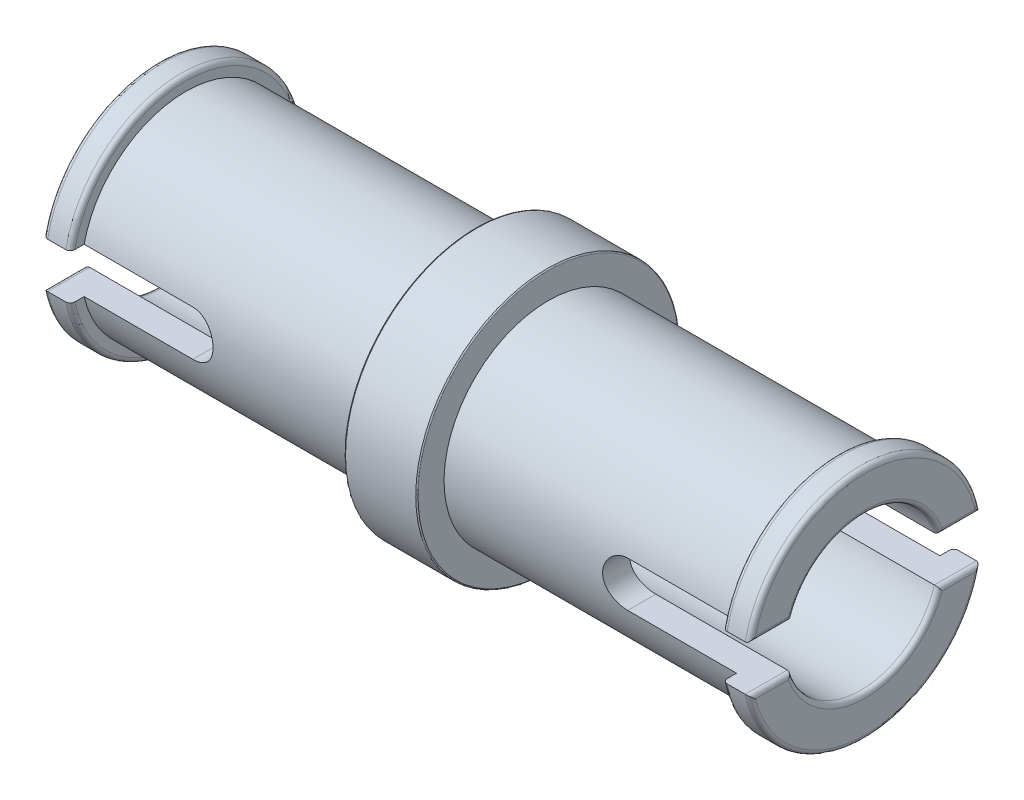
SolidWorks part; units mm, degrees
material "ABS"
ref_plane "Front Plane" through (0, 0, 0) normal (0, 0, 1) x (1, 0, 0)
ref_plane "Top Plane" through (0, 0, 0) normal (0, 1, 0) x (1, 0, 0)
ref_plane "Right Plane" through (0, 0, 0) normal (1, 0, 0) x (0, 0, -1)
sketch "Sketch1" plane through (0, 0, 0) normal (0, 0, 1) x (1, 0, 0)
  line L0 (0, 1.7) -> (0, 2.9)
  line L1 (0, 2.9) -> (-0.8, 2.9)
  line L2 (-0.8, 2.9) -> (-0.8, 2.3)
  line L3 (-0.8, 2.3) -> (-7.2, 2.3)
  line L4 (-7.2, 2.3) -> (-7.2, 2.6)
  line L5 (-7.2, 2.6) -> (-7.8, 2.6)
  line L6 (-7.8, 2.6) -> (-7.8, 1.7)
  line L7 (-7.8, 1.7) -> (0, 1.7)
  line L8 (0, 0) -> (0, 2.9) construction
  line L9 (0, 0) -> (-7.8, 0) construction
  dimension "D1" = 3.4
  dimension "D2" = 4.6
  dimension "D3" = 1.6
  dimension "D4" = 5.8
  dimension "D5" = 15.6
  dimension "D6" = 0.6
  dimension "D7" = 5.2
revolve "Revolve1" add sketch "Sketch1" angle 360 about L9
sketch "Sketch2" plane through (0, 0, 0) normal (0, 0, 1) x (1, 0, 0)
  line L0 (-7.8, 0.5) -> (-4.8, 0.5)
  line L1 (-4.8, -0.5) -> (-7.8, -0.5)
  line L2 (-7.8, -0.5) -> (-7.8, 0.5)
  line L3 (0, 0) -> (0, 3.3644) construction
  line L5 (-7.8, 2.6) -> (-7.8, -2.6) construction
  arc A0 (-4.8, 0.5) -> (-4.8, -0.5) centre (-4.8, 0) cw
  dimension "D1" = 8.6
  dimension "D2" = 1
extrude "Cut-Extrude1" cut sketch "Sketch2" against normal through all both and the other way through all
sketch "Sketch4" plane through (0, 0, 0) normal (0, 1, 0) x (1, 0, 0)
  line L0 (0, 0.5) -> (-2.9, 0.5)
  line L1 (0, -2.9) -> (0, 2.9) construction
  line L2 (-2.9, -0.5) -> (0, -0.5)
  line L3 (0, -0.5) -> (0, 0.5)
  line L4 (0, 0) -> (0, 3.4064) construction
  arc A0 (-2.9, 0.5) -> (-2.9, -0.5) centre (-2.9, 0) ccw
  dimension "D1" = 6.8
  dimension "D2" = 1
extrude "Cut-Extrude2" [suppressed] cut sketch "Sketch4" against normal through all both and the other way through all
ref_plane "Plane1" through (0, 0, 0) normal (0, -0.7071, 0.7071) x (1, 0, 0)
sketch "Sketch3" plane through (0, 0, 0) normal (0, -0.7071, 0.7071) x (1, 0, 0)
  line L0 (-7.2, -2.3) -> (-7.2, 1.2339) construction
  line L1 (-7.2, 0.4) -> (-5.6, 0.4)
  line L2 (-7.2, 0.4) -> (-7.2, -0.4)
  line L3 (-7.2, -0.4) -> (-5.6, -0.4)
  line L4 (-5.6, 0.4) -> (-5.6, -0.4)
  line L5 (-0.8, 2.9) -> (-0.8, -2.9) construction
  line L6 (-0.8, 0.4) -> (-2, 0.4)
  line L7 (-0.8, 0.4) -> (-0.8, -0.4)
  line L8 (-0.8, -0.4) -> (-2, -0.4)
  line L9 (-2, 0.4) -> (-2, -0.4)
  point P6 (-5.6, 0)
  dimension "D1" = 0.8
  dimension "D2" = 1.6
  dimension "D3" = 1.2
extrude "Boss-Extrude1" [suppressed] add sketch "Sketch3" along normal up to surface (0.3041 mm away) from surface
fillet "Fillet1" [suppressed] radius 0.2
fillet "Fillet2" [suppressed] radius 0.025
pattern_circular "CirPattern1" [suppressed] count 4 over 360 of bodies 105
fillet "Fillet3" radius 0.1 8 edges at (-7.8, -2.6, 0) (-7.8, 2.6, 0) (-7.8, 1.7, 0) (-7.8, -1.7, 0) (-7.8, -0.5, 2.0881) (-7.8, 0.5, 2.0881) (-7.8, 0.5, -2.0881) (-7.8, -0.5, -2.0881)
fillet "Fillet4" [suppressed] radius 0.025
fillet "Fillet5" radius 0.025 1 edges at (-0.8, 2.9, 0)
fillet "Fillet6" [suppressed] radius 0.1
fillet "Fillet7" radius 0.1 2 edges at (-7.2, 2.6, 0) (-7.2, -2.6, 0)
mirror "Mirror1" about plane through (0, 1.7, 0) normal (1, 0, 0) of bodies 104 107
